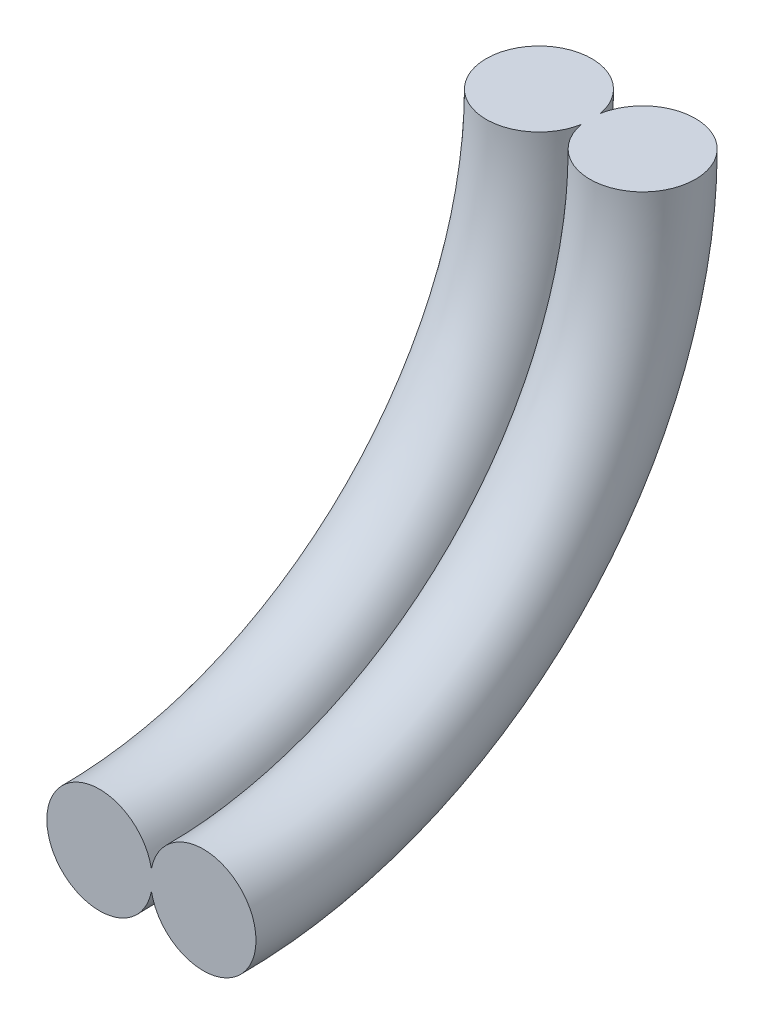
SolidWorks part; units mm, degrees
ref_plane "Front Plane" through (0, 0, 0) normal (0, 0, 1) x (1, 0, 0)
ref_plane "Top Plane" through (0, 0, 0) normal (0, 1, 0) x (1, 0, 0)
ref_plane "Right Plane" through (0, 0, 0) normal (1, 0, 0) x (0, 0, -1)
sketch "Sketch1" plane through (0, 0, 0) normal (0, 1, 0) x (1, 0, 0)
  line L0 (0, 0) -> (0, 0.6785) construction
  circle A0 centre (0.7493, 0) radius 0.762
  dimension "D1" = 1.524
  dimension "D2" = 1.4986
ref_plane "Plane1" through (0.2794, 0, 0) normal (1, 0, 0) x (0, 0, -1)
sketch "Sketch3" plane through (0.2794, 0, 0) normal (1, 0, 0) x (0, 0, -1)
  line L0 (0, 0) -> (0, 4.2593) construction
  arc A0 (0, 0) -> (-6.35, -6.35) centre (-6.35, 0) cw
  dimension "D1" = 6.35
  dimension "D2" = 6.35
sweep "Sweep2" add profiles "Sketch1" path "Sketch3"
mirror "Mirror4" about plane through (0, 0, 0) normal (1, 0, 0) of "Sweep2"
ref_axis "Axis1" through (0, 0.3315, 0) along (0, -1, 0)
equation "\"D2@Sketch3\"=\"D1@Sketch3\""
equation "\"D2@Sketch1\"=\"D1@Sketch1\"-0.001"
